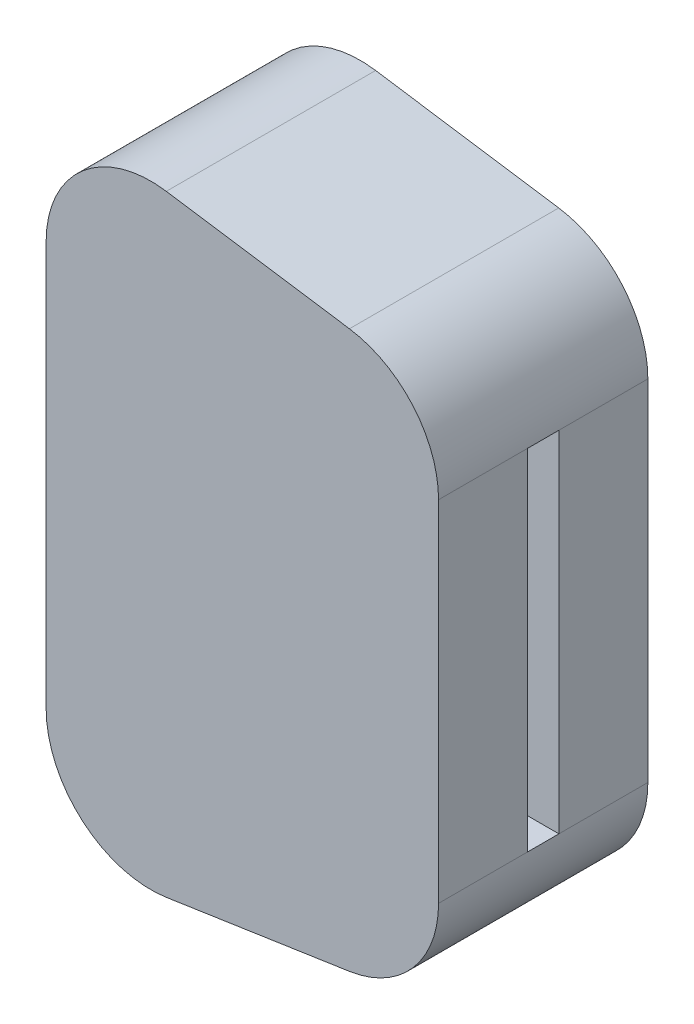
SolidWorks part; units mm, degrees
material "Polyurethane Foam Rigid"
ref_plane "Front Plane" through (0, 0, 0) normal (0, 0, 1) x (1, 0, 0)
ref_plane "Top Plane" through (0, 0, 0) normal (0, 1, 0) x (1, 0, 0)
ref_plane "Right Plane" through (0, 0, 0) normal (1, 0, 0) x (0, 0, -1)
sketch "Sketch1" plane through (0, 0, 0) normal (0, 0, 1) x (1, 0, 0)
  line L0 (0, 72.2334) -> (0, -72.2334) construction
  line L1 (0, 19.3256) -> (0, -19.3256)
  line L2 (-50, 0) -> (50, 0) construction
  line L3 (11.4834, 29.215) -> (28.9834, 26.59)
  line L4 (37.5, -16.7006) -> (37.5, 16.7006)
  line L5 (28.9834, -26.59) -> (11.4834, -29.215)
  arc A0 (28.9834, -26.59) -> (37.5, -16.7006) centre (27.5, -16.7006) ccw
  arc A1 (28.9834, 26.59) -> (37.5, 16.7006) centre (27.5, 16.7006) cw
  arc A2 (0, -19.3256) -> (11.4834, -29.215) centre (10, -19.3256) ccw
  arc A3 (0, 19.3256) -> (11.4834, 29.215) centre (10, 19.3256) cw
  point P13 (37.5, 0)
  point P14 (37.5, -25.3125)
  point P17 (37.5, 25.3125)
  point P20 (0, -30.9375)
  point P23 (0, 30.9375)
  point P24 (26.9612, 0)
  dimension "D4" = 10
  dimension "D5" = 10
  dimension "D1" = 37.5
  dimension "D2" = 61.875
  dimension "D3" = 50.625
extrude "Boss-Extrude1" add sketch "Sketch1" along normal blind 20
sketch "Sketch5" plane through (0, 0, 0) normal (-1, 0, 0) x (0, 0, 1)
  line L0 (10, 19.3256) -> (10, -19.3256) construction
  line L3 (20, 19.3256) -> (0, 19.3256) construction
  line L4 (20, -19.3256) -> (0, -19.3256) construction
  line L5 (5.5, 15.8428) -> (14.5, 15.8428)
  line L6 (5.5, 15.8428) -> (5.5, 17.2971)
  line L7 (5.5, 17.2971) -> (14.5, 17.2971)
  line L8 (14.5, 17.2971) -> (14.5, 15.8428)
  point P8 (10, 15.8428)
  point P9 (10, 17.2971)
  dimension "D1" = 9
extrude "Cut-Extrude4" cut sketch "Sketch5" against normal blind 10
sketch "Sketch6" plane through (0, 17.2971, 0) normal (0, -1, 0) x (1, 0, 0)
  line L0 (0, 10) -> (10.2544, 10) construction
  line L1 (0, 14.5) -> (0, 5.5) construction
  circle A0 centre (2.6449, 10) radius 0.5
extrude "Cut-Extrude5" cut sketch "Sketch6" against normal blind 5
sketch "Sketch7" plane through (37.5, 0, 0) normal (1, 0, 0) x (0, 0, -1)
  line L0 (-10, 16.7006) -> (-10, -16.7006) construction
  line L1 (-20, 16.7006) -> (0, 16.7006) construction
  line L2 (-20, -16.7006) -> (0, -16.7006) construction
  line L3 (-11.5, -16.7006) -> (-8.5, -16.7006)
  line L4 (-8.5, -16.7006) -> (-8.5, 16.7006)
  line L5 (-8.5, 16.7006) -> (-11.5, 16.7006)
  line L6 (-10, -16.7006) -> (-8.5, -16.7006)
  line L7 (-11.5, -16.7006) -> (-11.5, 16.7006)
  line M7 (0, 16.7006) -> (-20, 16.7006)
  line M9 (-20, -16.7006) -> (0, -16.7006)
  dimension "D1" = 1.5
  dimension "D2" = 1.5
extrude "Cut-Extrude7" cut sketch "Sketch7" against normal blind 23 contours L0 L5 L7 M9 | L0 L3 L4 M7 region at (37.5, 0, 9.25) region at (37.5, 0, 10.75)
